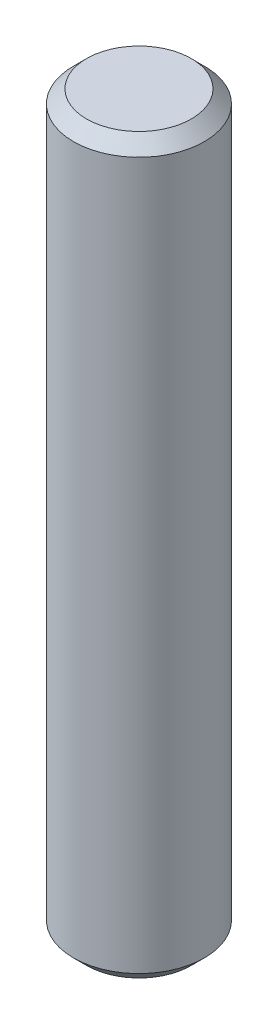
SolidWorks part; units mm, degrees
ref_plane "Ebene vorne" through (0, 0, 0) normal (0, 0, 1) x (1, 0, 0)
ref_plane "Ebene oben" through (0, 0, 0) normal (0, 1, 0) x (1, 0, 0)
ref_plane "Ebene rechts" through (0, 0, 0) normal (1, 0, 0) x (0, 0, -1)
sketch "Skizze1" plane through (0, 0, 0) normal (0, 1, 0) x (1, 0, 0)
  circle A0 centre (0, 0) radius 2.5
  dimension "D1" = 5
extrude "Aufsatz-Linear austragen1" add sketch "Skizze1" along normal blind 14 and the other way blind 14
chamfer "Fase1" distance 0.5 angle 45 2 edges at (0, -14, 2.5) (0, 14, 2.5)
ref_axis "Achse1" through (0, 6.9708, 0) along (0, -1, 0)
